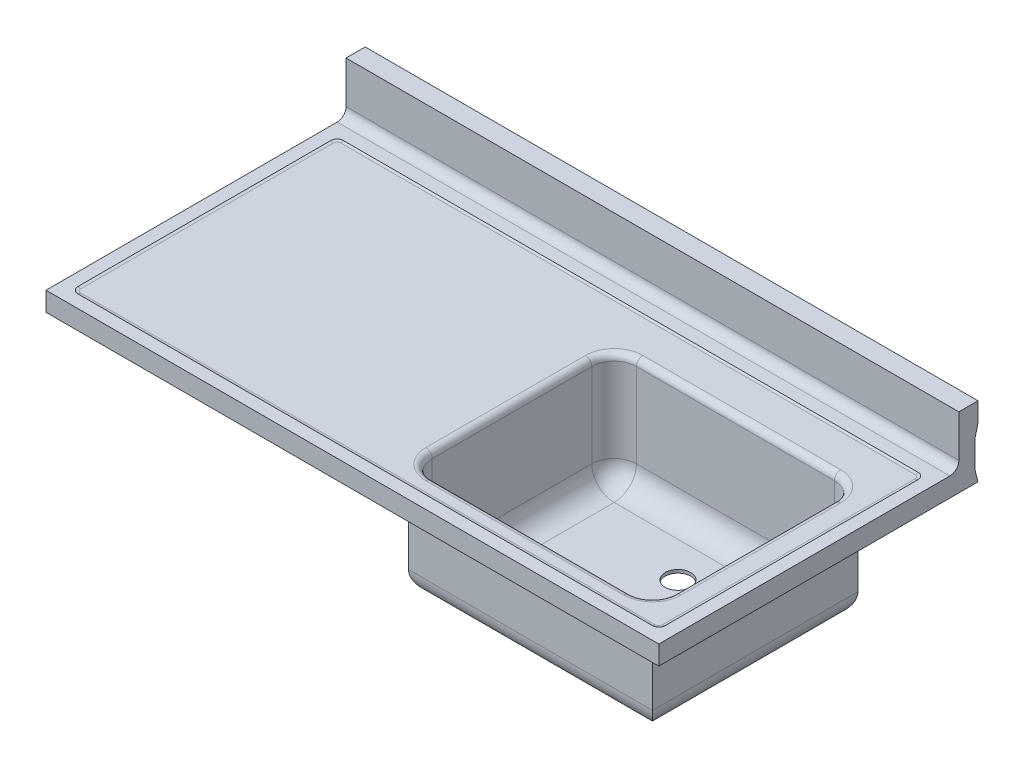
SolidWorks part; units mm, degrees
material "AISI 304"
ref_plane "Front Plane" through (0, 0, 0) normal (0, 0, 1) x (1, 0, 0)
ref_plane "Top Plane" through (0, 0, 0) normal (0, 1, 0) x (1, 0, 0)
ref_plane "Right Plane" through (0, 0, 0) normal (1, 0, 0) x (0, 0, -1)
sketch "Sketch1" plane through (0, 0, 0) normal (0, 1, 0) x (1, 0, 0)
  line L1 (-609.6, -317.5) -> (609.6, -317.5)
  line L2 (-609.6, -317.5) -> (-609.6, 317.5)
  line L3 (-609.6, 317.5) -> (609.6, 317.5)
  line L4 (609.6, -317.5) -> (609.6, 317.5)
  line L5 (-609.6, -317.5) -> (609.6, 317.5) construction
  line L6 (-609.6, 317.5) -> (609.6, -317.5) construction
  point P0 (0, 0)
  point P6 (-304.8, -38.1)
  dimension "D1" = 1219.2
  dimension "D2" = 635
extrude "Boss-Extrude2" add sketch "Sketch1" along normal blind 330.2
sketch "Sketch3" plane through (0, 0, 317.5) normal (0, 0, 1) x (1, 0, 0)
  line L0 (-609.6, 330.2) -> (-609.6, 0) construction
  line L1 (-609.6, 228.6) -> (609.6, 228.6)
  line L2 (-609.6, 228.6) -> (-609.6, 330.2)
  line L3 (-609.6, 330.2) -> (609.6, 330.2)
  line L4 (609.6, 228.6) -> (609.6, 330.2)
  line L5 (-609.6, 228.6) -> (609.6, 330.2) construction
  line L6 (-609.6, 330.2) -> (609.6, 228.6) construction
  point P0 (0, 279.4)
  dimension "D1" = 101.6
extrude "Cut-Extrude1" cut sketch "Sketch3" against normal blind 596.9
fillet "Fillet2" radius 17.78 1 edges at (0, 228.6, -279.4)
sketch "Sketch5" plane through (0, 228.6, 0) normal (0, 1, 0) x (1, 0, 0)
  line L1 (95.25, 152.4) -> (488.95, 152.4)
  line L2 (50.8, 107.95) -> (50.8, -209.55)
  line L3 (95.25, -254) -> (488.95, -254)
  line L4 (533.4, 107.95) -> (533.4, -209.55)
  line L5 (50.8, 152.4) -> (533.4, -254) construction
  line L6 (50.8, -254) -> (533.4, 152.4) construction
  line L7 (-609.6, -317.5) -> (609.6, -317.5) construction
  line L8 (-609.6, 261.62) -> (-609.6, -317.5) construction
  arc A0 (488.95, 152.4) -> (533.4, 107.95) centre (488.95, 107.95) cw
  arc A1 (488.95, -254) -> (533.4, -209.55) centre (488.95, -209.55) ccw
  arc A2 (50.8, -209.55) -> (95.25, -254) centre (95.25, -209.55) ccw
  arc A3 (50.8, 107.95) -> (95.25, 152.4) centre (95.25, 107.95) cw
  point P0 (292.1, -50.8)
  dimension "D5" = 44.45
  dimension "D1" = 482.6
  dimension "D2" = 406.4
  dimension "D3" = 660.4
  dimension "D4" = 63.5
extrude "Cut-Extrude2" cut sketch "Sketch5" against normal blind 226.06
fillet "Fillet4" radius 44.45 8 edges at (533.4, 2.54, 50.8) (520.3809, 2.54, 240.9809) (292.1, 2.54, 254) (63.8191, 2.54, 240.9809) (50.8, 2.54, 50.8) (63.8191, 2.54, -139.3809) (292.1, 2.54, -152.4) (520.3809, 2.54, -139.3809)
sketch "Sketch7" plane through (0, 228.6, 0) normal (0, 1, 0) x (1, 0, 0)
  line L0 (-609.6, 261.62) -> (-609.6, -317.5) construction
  line L1 (-571.5, -292.1) -> (571.5, -292.1)
  line L2 (-584.2, -279.4) -> (-584.2, 223.52)
  line L3 (-571.5, 236.22) -> (571.5, 236.22)
  line L4 (584.2, -279.4) -> (584.2, 223.52)
  line L5 (-584.2, -292.1) -> (584.2, 236.22) construction
  line L6 (-584.2, 236.22) -> (584.2, -292.1) construction
  line L7 (-609.6, -317.5) -> (609.6, -317.5) construction
  line L8 (609.6, 261.62) -> (609.6, -317.5) construction
  line L9 (609.6, 261.62) -> (-609.6, 261.62) construction
  arc A0 (584.2, -279.4) -> (571.5, -292.1) centre (571.5, -279.4) cw
  arc A1 (584.2, 223.52) -> (571.5, 236.22) centre (571.5, 223.52) ccw
  arc A2 (-584.2, -279.4) -> (-571.5, -292.1) centre (-571.5, -279.4) ccw
  arc A3 (-571.5, 236.22) -> (-584.2, 223.52) centre (-571.5, 223.52) ccw
  point P0 (0, -27.94)
  dimension "D5" = 12.7
  dimension "D1" = 25.4
  dimension "D2" = 25.4
  dimension "D3" = 25.4
  dimension "D4" = 25.4
extrude "Cut-Extrude3" cut sketch "Sketch7" against normal blind 1.27
fillet "Fillet5" radius 12.7 16 edges at (520.3809, 227.33, -139.3809) (292.1, 227.33, -152.4) (63.8191, 227.33, -139.3809) (50.8, 227.33, 50.8) (63.8191, 227.33, 240.9809) (292.1, 227.33, 254) (520.3809, 227.33, 240.9809) (533.4, 227.33, 50.8) (0, 227.33, 292.1) (-580.4803, 227.33, 288.3803) (-584.2, 227.33, 27.94) (-580.4803, 227.33, -232.5003) (0, 227.33, -236.22) (580.4803, 227.33, -232.5003) (584.2, 227.33, 27.94) (580.4803, 227.33, 288.3803)
sketch "Sketch9" plane through (0, 0, 0) normal (1, 0, 0) x (0, 0, -1)
  line L0 (317.5, 226.06) -> (198.12, 226.06)
  line L1 (317.5, 330.2) -> (317.5, 0) construction
  line L2 (153.67, 181.61) -> (153.67, 45.72)
  line L3 (109.22, 1.27) -> (-210.82, 1.27)
  line L4 (-255.27, 45.72) -> (-255.27, 181.61)
  line L5 (-299.72, 226.06) -> (-316.23, 226.06)
  line L7 (-317.5, 190.5) -> (-317.5, 0)
  line L8 (-317.5, 0) -> (317.5, 0)
  line L9 (317.5, 0) -> (317.5, 226.06)
  line L10 (261.62, 228.6) -> (-317.5, 228.6) construction
  line L11 (-316.23, 226.06) -> (-316.23, 190.5)
  line L12 (-316.23, 190.5) -> (-317.5, 190.5)
  line L13 (-317.5, 228.6) -> (-317.5, 0) construction
  arc A0 (-299.72, 226.06) -> (-255.27, 181.61) centre (-299.72, 181.61) cw
  arc A1 (-255.27, 45.72) -> (-210.82, 1.27) centre (-210.82, 45.72) ccw
  arc A2 (109.22, 1.27) -> (153.67, 45.72) centre (109.22, 45.72) ccw
  arc A3 (198.12, 226.06) -> (153.67, 181.61) centre (198.12, 181.61) ccw
  dimension "D5" = 44.45
  dimension "D1" = 2.54
  dimension "D2" = 1.27
  dimension "D3" = 408.94
  dimension "D4" = 62.23
  dimension "D6" = 1.27
  dimension "D7" = 38.1
extrude "Cut-Extrude4" cut sketch "Sketch9" against normal mid plane 1216.66
sketch "Sketch10" plane through (0, 0, 317.5) normal (0, 0, 1) x (1, 0, 0)
  line L0 (-609.6, 226.06) -> (-579.12, 226.06)
  line L1 (-609.6, 228.6) -> (-609.6, 0) construction
  line L2 (-534.67, 181.61) -> (-534.67, 45.72)
  line L3 (-490.22, 1.27) -> (-93.98, 1.27)
  line L4 (-49.53, 45.72) -> (-49.53, 181.61)
  line L5 (-5.08, 226.06) -> (609.6, 226.06)
  line L6 (609.6, 228.6) -> (609.6, 0) construction
  line L7 (609.6, 226.06) -> (609.6, 0)
  line L8 (609.6, 0) -> (-609.6, 0)
  line L9 (-609.6, 0) -> (-609.6, 226.06)
  line L10 (-609.6, 228.6) -> (609.6, 228.6) construction
  arc A0 (-5.08, 226.06) -> (-49.53, 181.61) centre (-5.08, 181.61) ccw
  arc A1 (-49.53, 45.72) -> (-93.98, 1.27) centre (-93.98, 45.72) cw
  arc A2 (-490.22, 1.27) -> (-534.67, 45.72) centre (-490.22, 45.72) cw
  arc A3 (-579.12, 226.06) -> (-534.67, 181.61) centre (-579.12, 181.61) cw
  dimension "D4" = 44.45
  dimension "D1" = 1.27
  dimension "D2" = 485.14
  dimension "D3" = 2.54
  dimension "D5" = 74.93
sketch "Sketch11" plane through (0, 0, 0) normal (0, 0, 1) x (1, 0, 0)
  line L0 (-608.33, 226.06) -> (5.08, 226.06)
  line L1 (49.53, 181.61) -> (49.53, 45.72)
  line L3 (534.67, 45.72) -> (534.67, 181.61)
  line L4 (579.12, 226.06) -> (608.33, 226.06)
  line L5 (608.33, 226.06) -> (608.33, 1.27)
  line L6 (608.33, 1.27) -> (490.22, 1.27)
  line L7 (-608.33, 1.27) -> (-608.33, 226.06)
  line L8 (93.98, 1.27) -> (-608.33, 1.27)
  line L9 (609.6, 228.6) -> (-609.6, 228.6) construction
  line L10 (-609.6, 0) -> (-609.6, 226.06) construction
  line L11 (609.6, 226.06) -> (609.6, 0) construction
  line L12 (-608.33, 1.27) -> (608.33, 1.27) construction
  arc A0 (579.12, 226.06) -> (534.67, 181.61) centre (579.12, 181.61) ccw
  arc A1 (534.67, 45.72) -> (490.22, 1.27) centre (490.22, 45.72) cw
  arc A2 (93.98, 1.27) -> (49.53, 45.72) centre (93.98, 45.72) cw
  arc A3 (5.08, 226.06) -> (49.53, 181.61) centre (5.08, 181.61) cw
  dimension "D3" = 44.45
  dimension "D1" = 44.45
  dimension "D2" = 485.14
  dimension "D4" = 657.86
  dimension "D5" = 2.54
  dimension "D6" = 1.27
  dimension "D7" = 1.27
  dimension "D8" = 44.45
extrude "Cut-Extrude6" cut sketch "Sketch11" against normal mid plane 632.46
sketch "Sketch12" plane through (-609.6, 0, 0) normal (-1, 0, 0) x (0, 0, 1)
  line L0 (-261.62, 228.6) -> (317.5, 228.6) construction
  line L1 (-317.5, 190.5) -> (317.5, 190.5)
  line L2 (-317.5, 190.5) -> (-317.5, 0)
  line L3 (-317.5, 0) -> (317.5, 0)
  line L4 (317.5, 190.5) -> (317.5, 0)
  line L5 (-317.5, 190.5) -> (317.5, 0) construction
  line L6 (-317.5, 0) -> (317.5, 190.5) construction
  line L7 (-317.5, 330.2) -> (-317.5, 0) construction
  point P0 (0, 95.25)
  dimension "D1" = 38.1
extrude "Cut-Extrude7" cut sketch "Sketch12" against normal blind 2.54
sketch "Sketch13" plane through (609.6, 0, 0) normal (1, 0, 0) x (0, 0, -1)
  line L0 (261.62, 228.6) -> (-317.5, 228.6) construction
  line L1 (-317.5, 190.5) -> (317.5, 190.5)
  line L2 (-317.5, 190.5) -> (-317.5, 0)
  line L3 (-317.5, 0) -> (317.5, 0)
  line L4 (317.5, 190.5) -> (317.5, 0)
  line L5 (-317.5, 190.5) -> (317.5, 0) construction
  line L6 (-317.5, 0) -> (317.5, 190.5) construction
  line L7 (-317.5, 228.6) -> (-317.5, 0) construction
  point P0 (0, 95.25)
  dimension "D1" = 38.1
extrude "Cut-Extrude8" cut sketch "Sketch13" against normal blind 2.54
sketch "Sketch15" plane through (0, 2.54, 0) normal (0, 1, 0) x (1, 0, 0)
  line L0 (609.6, 317.5) -> (-609.6, 317.5) construction
  line L1 (95.25, 165.1) -> (488.95, 165.1) construction
  circle A0 centre (292.1, 38.1) radius 25.4
  point P7 (292.1, 165.1)
  dimension "D1" = 279.4
  dimension "D2" = 50.8
ref_plane "Plane1" through (292.1, 0, 0) normal (1, 0, 0) x (0, 0, -1)
sketch "Sketch16" plane through (292.1, 0, 0) normal (1, 0, 0) x (0, 0, -1)
  line L5 (38.1, 1.27) -> (38.1, -3.81)
  line L6 (109.22, 1.27) -> (-210.82, 1.27) construction
  line L7 (38.1, -3.81) -> (77.47, -3.81)
  line L8 (95.25, 1.1782) -> (95.25, 1.27)
  line L9 (95.25, 1.27) -> (38.1, 1.27)
  arc A0 (95.25, 1.1782) -> (77.47, -3.81) centre (98.1051, -43.18) ccw
  dimension "D1" = 44.45
  dimension "D2" = 5.08
  dimension "D3" = 57.15
  dimension "D4" = 39.37
revolve "Revolve1" add sketch "Sketch16" angle 360 about L5
extrude "Cut-Extrude9" cut sketch "Sketch15" against normal up to surface (6.35 mm away) contours A0 up to face at (292.1, -3.81, 1.27)
sketch "Sketch17" plane through (609.6, 0, 0) normal (1, 0, 0) x (0, 0, -1)
  line L0 (317.5, 292.1) -> (311.15, 266.7)
  line L1 (317.5, 330.2) -> (317.5, 190.5) construction
  line L2 (311.15, 266.7) -> (311.15, 215.9)
  line L3 (311.15, 215.9) -> (317.5, 190.5)
  line L4 (317.5, 292.1) -> (317.5, 190.5)
  dimension "D1" = 6.35
  dimension "D2" = 25.4
  dimension "D3" = 25.4
  dimension "D4" = 50.8
extrude "Cut-Extrude10" cut sketch "Sketch17" against normal up to surface (1219.2 mm away) up to face at (-609.6, 248.7568, -117.7289)
